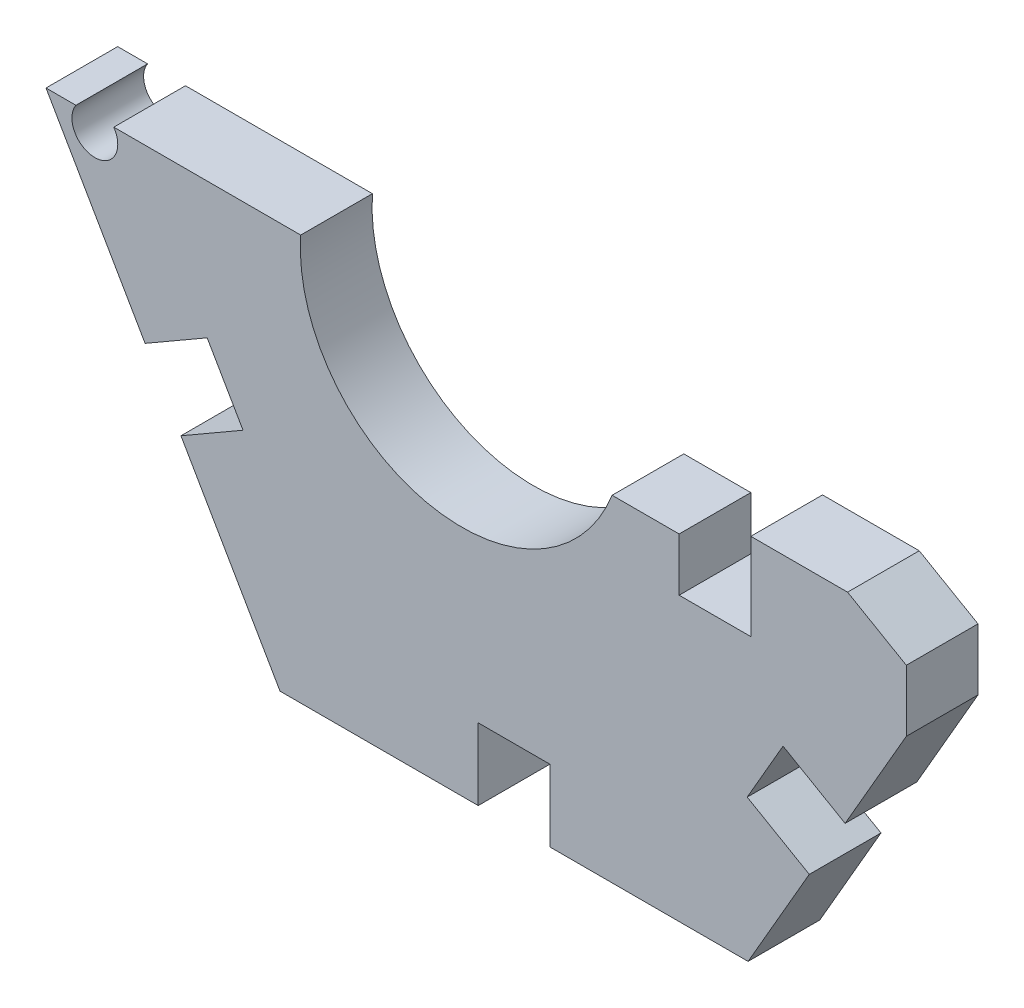
SolidWorks part; units mm, degrees
ref_plane "Front Plane" through (0, 0, 0) normal (0, 0, 1) x (1, 0, 0)
ref_plane "Top Plane" through (0, 0, 0) normal (0, 1, 0) x (1, 0, 0)
ref_plane "Right Plane" through (0, 0, 0) normal (1, 0, 0) x (0, 0, -1)
sketch "Sketch1" plane through (0, 0, 0) normal (0, 0, 1) x (1, 0, 0)
  line L0 (-1.524, -3.3705) -> (-1.524, -2.2428)
  line L1 (-1.524, -2.2428) -> (-2.9489, -2.2428)
  line L2 (-1.524, -3.3705) -> (0, -3.3705)
  line L3 (0, -3.3705) -> (0, -1.524)
  line L4 (-9.5684, -0.762) -> (-13.5425, -0.762)
  line L5 (-14.3477, -0.762) -> (-14.9835, -0.762)
  line L6 (-14.9835, -0.762) -> (-12.8769, -4.4107)
  line L8 (2.0566, -1.524) -> (0, -1.524)
  line L9 (2.0566, -1.524) -> (3.3055, -2.2451)
  line L10 (-14.1036, -0.762) -> (-9.5684, -8.6173) construction
  line L11 (-9.5684, -8.6173) -> (-0.4979, -8.6173) construction
  line L12 (-0.4979, -8.6173) -> (3.2122, -2.1912) construction
  line L13 (-10.0083, -9.3793) -> (-5.7951, -9.3793)
  line L14 (-0.0579, -9.3793) -> (1.2428, -7.1263)
  line L15 (-13.2238, -0.762) -> (-9.1285, -7.8553) construction
  line L16 (-9.1285, -7.8553) -> (-0.9378, -7.8553) construction
  line L17 (1.6238, -6.4664) -> (0.304, -5.7044) construction
  line L18 (-12.4959, -5.0706) -> (-11.1761, -4.3086) construction
  line L19 (-12.1149, -5.7306) -> (-10.7951, -4.9686)
  line L20 (-0.9378, -7.8553) -> (2.5523, -1.8102) construction
  line L21 (-5.7951, -7.8553) -> (-5.7951, -9.3793)
  line L22 (3.3055, -2.2451) -> (2.5523, -1.8102)
  line L23 (3.3055, -3.5535) -> (3.3055, -2.2451)
  line L24 (2.0048, -5.8065) -> (0.685, -5.0445)
  line L25 (-0.9378, -7.8553) -> (0.382, -8.6173) construction
  line L26 (-12.8769, -4.4107) -> (-11.5571, -3.6487)
  line L27 (-5.0331, -7.8553) -> (-5.0331, -9.3793) construction
  line L28 (-9.1285, -7.8553) -> (-10.4483, -8.6173) construction
  line L29 (-9.1285, -7.8553) -> (-9.1285, -9.3793) construction
  line L30 (-0.9378, -7.8553) -> (-0.9378, -9.3793) construction
  line L31 (-4.2711, -7.8553) -> (-4.2711, -9.3793)
  line L32 (1.2428, -7.1263) -> (-0.077, -6.3643)
  line L34 (-10.7951, -4.9686) -> (-11.5571, -3.6487)
  line L35 (-5.7951, -7.8553) -> (-4.2711, -7.8553)
  line L36 (-12.1149, -5.7306) -> (-10.0083, -9.3793)
  line L37 (-4.2711, -9.3793) -> (-0.0579, -9.3793)
  line L38 (0.685, -5.0445) -> (-0.077, -6.3643)
  line L39 (2.0048, -5.8065) -> (3.3055, -3.5535)
  arc A0 (-14.3477, -0.762) -> (-13.5425, -0.762) centre (-13.9451, -1.0366) ccw
  arc A1 (-2.9489, -2.2428) -> (-9.5684, -0.762) centre (-6.146, -0.9986) cw
  point P17 (3.8721, -2.5722)
  point P20 (-13.4437, -0.381)
extrude "Boss-Extrude1" add sketch "Sketch1" along normal blind 1.524 contours L9 L8 L3 L2 L0 L1 A1 L4 A0 L5 L6 L26 L34 L19 L36 L13 L21 L35 L31 L37 L14 L32 L38 L24 L39 L23
